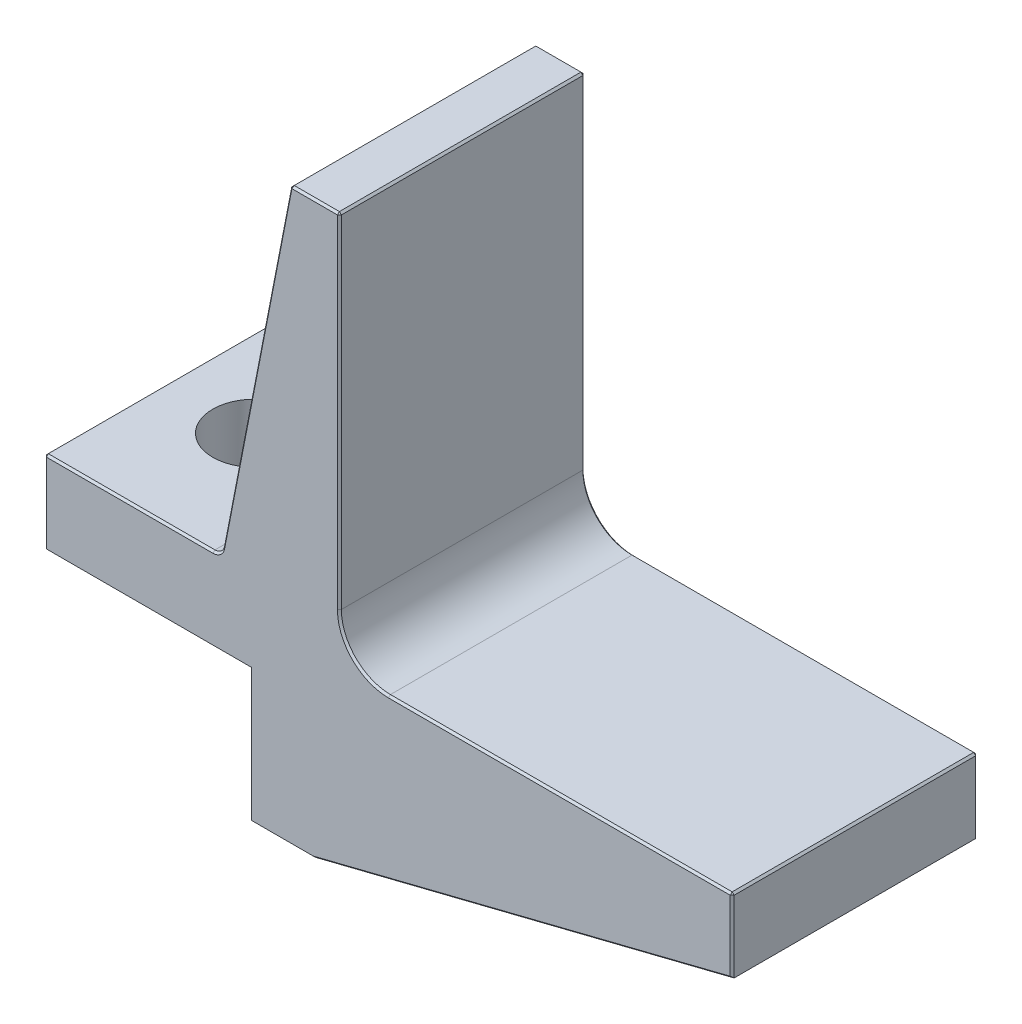
SolidWorks part; units mm, degrees
other "Markup1"
sketch "Sketch7" plane through (-38.1608, 50.8, 31.75) normal (-0.1424, 0.1459, 0.979) x (0.9898, 0.0098, 0.1425)
material "7075-T6 (SN)"
ref_plane "Front Plane" through (0, 0, 0) normal (0, 0, 1) x (1, 0, 0)
ref_plane "Top Plane" through (0, 0, 0) normal (0, 1, 0) x (1, 0, 0)
ref_plane "Right Plane" through (0, 0, 0) normal (1, 0, 0) x (0, 0, -1)
sketch "Sketch1" plane through (0, 0, 0) normal (0, 0, 1) x (1, 0, 0)
  line L0 (0, 0) -> (50.8, 0)
  line L1 (50.8, 0) -> (50.8, -9.525)
  line L2 (-11.6178, -5.9413) -> (-38.1608, -5.9413)
  line L3 (-38.1608, -5.9413) -> (-38.1608, 4.8537)
  line L4 (-38.1608, 4.8537) -> (-15.3008, 4.8537)
  line L5 (-15.3008, 4.8537) -> (-6.35, 50.8)
  line L6 (-6.35, 50.8) -> (0, 50.8)
  line L7 (0, 50.8) -> (0, 0)
  line L8 (-11.6178, -5.9413) -> (-11.6178, -23.0863)
  line L9 (-11.6178, -23.0863) -> (-3.3628, -23.0863)
  line L10 (-3.3628, -23.0863) -> (50.8, -9.525)
  dimension "D1" = 50.8
  dimension "D2" = 50.8
  dimension "D3" = 9.525
  dimension "D4" = 38.1608
  dimension "D5" = 6.35
  dimension "D6" = 22.86
  dimension "D7" = 26.543
  dimension "D8" = 10.795
  dimension "D9" = 17.145
  dimension "D10" = 8.255
  dimension "D11" = 4.8537
extrude "Boss-Extrude1" add sketch "Sketch1" along normal blind 31.75
hole_wizard "3/8 (0.375) Diameter Hole1" positions "Sketch8" profile "Sketch3" hole size "3/8" standard "ANSI Inch" end condition through all
sketch "Sketch8" plane through (0, 4.8537, 0) normal (0, 1, 0) x (1, 0, 0)
  line L1 (-38.1608, -31.75) -> (-38.1608, 0) construction
  point P0 (-26.8578, -15.875)
  point P8 (-38.1608, -15.875)
  dimension "D1" = 11.303
sketch "Sketch3" plane through (-26.8578, 4.8537, 15.875) normal (1, 0, 0) x (0, 0, 1)
  line L0 (0, 0) -> (0, 27.94)
  line L1 (0, 27.94) -> (5.3975, 27.94)
  line L2 (5.3975, 27.94) -> (5.3975, 0)
  line L5 (5.3975, 0) -> (0, 0)
  line L11 (0, -6.35) -> (0, 107.95) construction
  dimension "Thru Hole Dia." = 10.795
  dimension "Thru Hole Depth" = 27.94
fillet "Fillet1" radius 1.27 1 edges at (-15.3008, 4.8537, 15.875)
fillet "Fillet2" radius 6.35 1 edges at (0, 0, 15.875)
chamfer "Chamfer1" distance 0.254 angle 45 31 edges at (-6.35, 50.8, 15.875) (-3.175, 50.8, 0) (-10.7254, 28.3404, 0) (-15.5397, 5.1436, 0) (-27.254, 4.8537, 0) (-38.1608, -0.5438, 0) (-24.8893, -5.9413, 0) (50.8, -4.7625, 0) (28.575, 0, 0) (1.8599, 1.8599, 0) (0, 28.575, 0) (50.8, -4.7625, 31.75) (-24.8893, -5.9413, 31.75) (-38.1608, -5.9413, 15.875) (-38.1608, -0.5438, 31.75) (-38.1608, 4.8537, 15.875) (-27.254, 4.8537, 31.75) (-15.5397, 5.1436, 31.75) (-10.7254, 28.3404, 31.75) (-3.175, 50.8, 31.75) (0, 50.8, 15.875) (0, 28.575, 31.75) (1.8599, 1.8599, 31.75) (28.575, 0, 31.75) (50.8, 0, 15.875) (-11.6178, -14.5138, 0) (-7.4903, -23.0863, 0) (23.7186, -16.3057, 0) (23.7186, -16.3057, 31.75) (-7.4903, -23.0863, 31.75) (-11.6178, -14.5138, 31.75) first distance on face at (-3.175, 50.8, 15.875) first distance on face at (-10.7254, 28.3404, 15.875) first distance on face at (-15.6318, 5.2554, 15.875) first distance on face at (-26.8578, 4.8537, 21.2725) first distance on face at (-38.1608, -0.5438, 15.875) first distance on face at (-32.2553, -5.9413, 15.875) first distance on face at (50.8, -4.7625, 15.875) first distance on face at (-2.6076, 4.1861, 0) first distance on face at (2.5174, 2.5174, 15.875) first distance on face at (0, 28.575, 15.875) first distance on face at (-2.6076, 4.1861, 31.75) first distance on face at (-11.6178, -14.5138, 15.875) first distance on face at (-7.4903, -23.0863, 15.875) first distance on face at (23.7186, -16.3057, 15.875)
